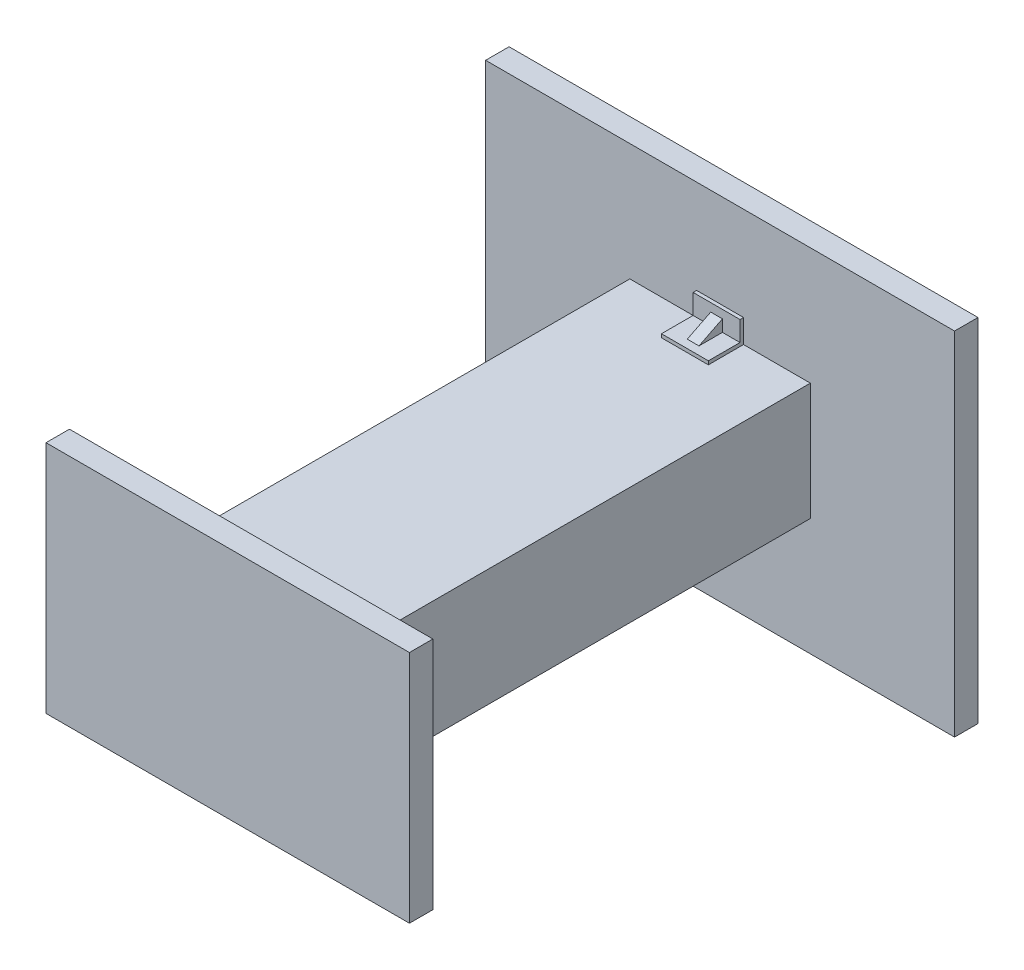
SolidWorks part; units mm, degrees
ref_plane "Front Plane" through (0, 0, 0) normal (0, 0, 1) x (1, 0, 0)
ref_plane "Top Plane" through (0, 0, 0) normal (0, 1, 0) x (1, 0, 0)
ref_plane "Right Plane" through (0, 0, 0) normal (1, 0, 0) x (0, 0, -1)
sketch "Sketch1" plane through (0, 0, 0) normal (0, 0, 1) x (1, 0, 0)
  line L1 (-77.5, -50) -> (77.5, -50)
  line L2 (-77.5, -50) -> (-77.5, 50)
  line L3 (-77.5, 50) -> (77.5, 50)
  line L4 (77.5, -50) -> (77.5, 50)
  line L5 (-77.5, -50) -> (77.5, 50) construction
  line L6 (-77.5, 50) -> (77.5, -50) construction
  point P0 (0, 0)
  dimension "D1" = 155
  dimension "D2" = 100
extrude "Boss-Extrude1" add sketch "Sketch1" along normal blind 10
sketch "Sketch5" plane through (0, 0, 0) normal (0, 0, -1) x (-1, 0, 0)
  line L1 (-38.5, -25) -> (38.5, -25)
  line L2 (-38.5, -25) -> (-38.5, 25)
  line L3 (-38.5, 25) -> (38.5, 25)
  line L4 (38.5, -25) -> (38.5, 25)
  line L5 (-38.5, -25) -> (38.5, 25) construction
  line L6 (-38.5, 25) -> (38.5, -25) construction
  point P0 (0, 0)
  dimension "D1" = 77
  dimension "D2" = 50
extrude "Boss-Extrude5" add sketch "Sketch5" along normal blind 200
sketch "Sketch6" plane through (0, 0, -200) normal (0, 0, -1) x (-1, 0, 0)
  line L5 (-100, -75) -> (100, -75)
  line L6 (-100, -75) -> (-100, 75)
  line L7 (-100, 75) -> (100, 75)
  line L8 (100, -75) -> (100, 75)
  line L9 (-100, -75) -> (100, 75) construction
  line L10 (-100, 75) -> (100, -75) construction
  point P0 (0, 0)
  point P1 (0, 0)
  dimension "D1" = 200
  dimension "D2" = 150
extrude "Boss-Extrude12" add sketch "Sketch6" along normal blind 10
ref_plane "Plane4" through (0, 0, -100) normal (0, 0, -1) x (-1, 0, 0)
sketch "Sketch7" plane through (0, 0, 0) normal (1, 0, 0) x (0, 0, -1)
  line L0 (15, -25) -> (0, -25)
  line L1 (200, -25) -> (0, -25) construction
  line L2 (0, -25) -> (0, -35)
  line L3 (0, -50) -> (0, 50) construction
  line L4 (0, -35) -> (1.5, -35)
  line L5 (1.5, -35) -> (1.5, -26.5)
  line L6 (1.5, -26.5) -> (15, -26.5)
  line L7 (15, -26.5) -> (15, -25)
  line L8 (11.5, -26.5) -> (1.5, -31.5)
  dimension "D1" = 15
  dimension "D2" = 10
  dimension "D3" = 1.5
  dimension "D4" = 1.5
  dimension "D5" = 10
  dimension "D6" = 5
extrude "Boss-Extrude13" add sketch "Sketch7" along normal mid plane 20 contours L6 L7 L0 L2 L4 L5 region at (0, -25.75, -14.8197)
extrude "Boss-Extrude14" add sketch "Sketch7<3>" along normal mid plane 5 contours L8 L6 L5 region at (0, -28.1667, -4.8333)
sketch "Sketch7<3>" plane through (0, 0, 0) normal (1, 0, 0) x (0, 0, -1) same geometry as "Sketch7"
ref_plane "Plane5" through (0, 0, -100) normal (0, 0, -1) x (-1, 0, 0)
mirror "Mirror1" about plane through (0, 0, 0) normal (0, 1, 0) of "Boss-Extrude14", "Boss-Extrude13"
mirror "Mirror2" about plane through (0, 0, -100) normal (0, 0, -1) of "Boss-Extrude14", "Boss-Extrude13", "Mirror1"
scale "Scale3" scale about centroid uniform scaling yes scale factor 2
